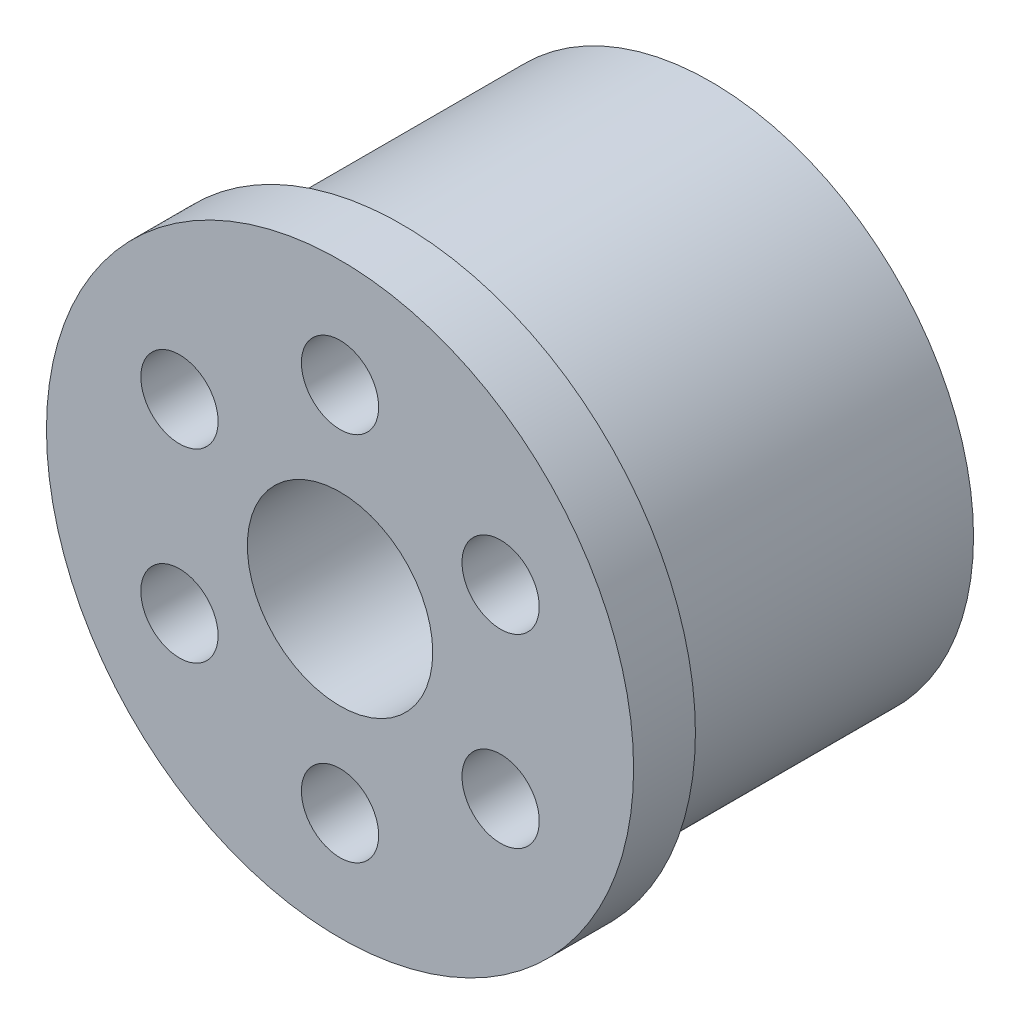
SolidWorks part; units mm, degrees
ref_plane "Front Plane" through (0, 0, 0) normal (0, 0, 1) x (1, 0, 0)
ref_plane "Top Plane" through (0, 0, 0) normal (0, 1, 0) x (1, 0, 0)
ref_plane "Right Plane" through (0, 0, 0) normal (1, 0, 0) x (0, 0, -1)
sketch "Sketch1" plane through (0, 0, 0) normal (0, 0, 1) x (1, 0, 0)
  circle A0 centre (0, 0) radius 3
  circle A1 centre (0, 0) radius 9.5
  circle A2 centre (0, -6) radius 1.25
  circle A3 centre (0, 0) radius 8.5
  circle A4 centre (0, 0) radius 7.5
  circle A5 centre (0, 0) radius 4.5
  dimension "D1" = 6
  dimension "D2" = 19
  dimension "D3" = 2.5
  dimension "D5" = 17
  dimension "D6" = 15
  dimension "D7" = 9
  dimension "D4" = 6
extrude "Boss-Extrude1" add sketch "Sketch1" along normal mid plane 12 contours A3 A4 | A5 A0 region at (-8.2596, 0, 0) region at (-4.3727, 0, 0)
extrude "Boss-Extrude12" add sketch "Sketch1<4>" against normal blind 2 from offset 6 contours A1 A3 | A4 A5 A2 | A2 region at (-9.2313, 0, 0) region at (0, -6, 0) region at (-7.2879, 0, 0)
sketch "Sketch1<4>" plane through (0, 0, 0) normal (0, 0, 1) x (1, 0, 0) same geometry as "Sketch1"
extrude "Cut-Extrude2" cut sketch "Sketch1<5>" against normal through all both and the other way through all contours A2
sketch "Sketch1<5>" plane through (0, 0, 0) normal (0, 0, 1) x (1, 0, 0) same geometry as "Sketch1"
pattern_circular "CirPattern1" count 6 over 360 about axis through (0, 0, 6) along (0, 0, 1) of "Cut-Extrude2"
